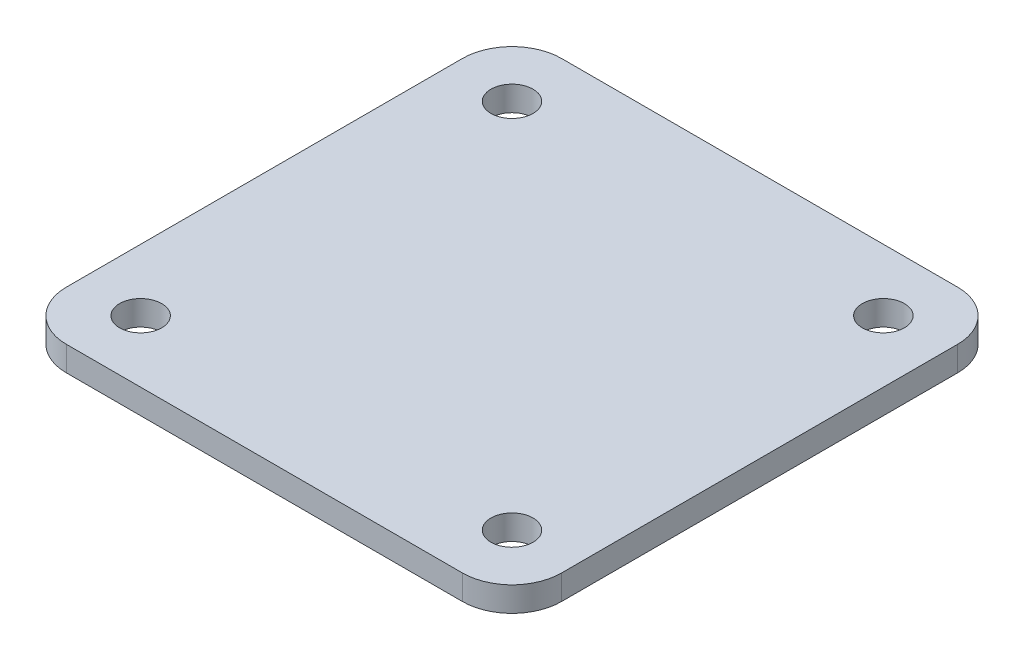
SolidWorks part; units mm, degrees
ref_plane "Front Plane" through (0, 0, 0) normal (0, 0, 1) x (1, 0, 0)
ref_plane "Top Plane" through (0, 0, 0) normal (0, 1, 0) x (1, 0, 0)
ref_plane "Right Plane" through (0, 0, 0) normal (1, 0, 0) x (0, 0, -1)
ref_axis "Axis1" through (0, 18.9, 0) along (0, -1, 0)
sketch "Sketch1" plane through (0, 0, 0) normal (0, 1, 0) x (1, 0, 0)
  line L1 (20, 20) -> (-20, 20)
  line L2 (20, 20) -> (20, -20)
  line L3 (20, -20) -> (-20, -20)
  line L4 (-20, 20) -> (-20, -20)
  line L5 (20, 20) -> (-20, -20) construction
  line L6 (20, -20) -> (-20, 20) construction
  point P0 (0, 0)
  dimension "D1" = 40
extrude "Boss-Extrude1" add sketch "Sketch1" along normal blind 2
sketch "Sketch2" plane through (0, 2, 0) normal (0, 1, 0) x (1, 0, 0)
  line L1 (-15, -15) -> (15, -15) construction
  line L2 (-15, -15) -> (-15, 15) construction
  line L3 (-15, 15) -> (15, 15) construction
  line L4 (15, -15) -> (15, 15) construction
  line L5 (-15, -15) -> (15, 15) construction
  line L6 (-15, 15) -> (15, -15) construction
  circle A0 centre (15, 15) radius 1.7
  circle A1 centre (15, -15) radius 1.7
  circle A2 centre (-15, -15) radius 1.7
  circle A3 centre (-15, 15) radius 1.7
  point P0 (0, 0)
  dimension "D2" = 3.4
  dimension "D1" = 30
extrude "Cut-Extrude1" cut sketch "Sketch2" against normal through all
fillet "Fillet1" radius 4 4 edges at (-20, 1, -20) (-20, 1, 20) (20, 1, 20) (20, 1, -20)
